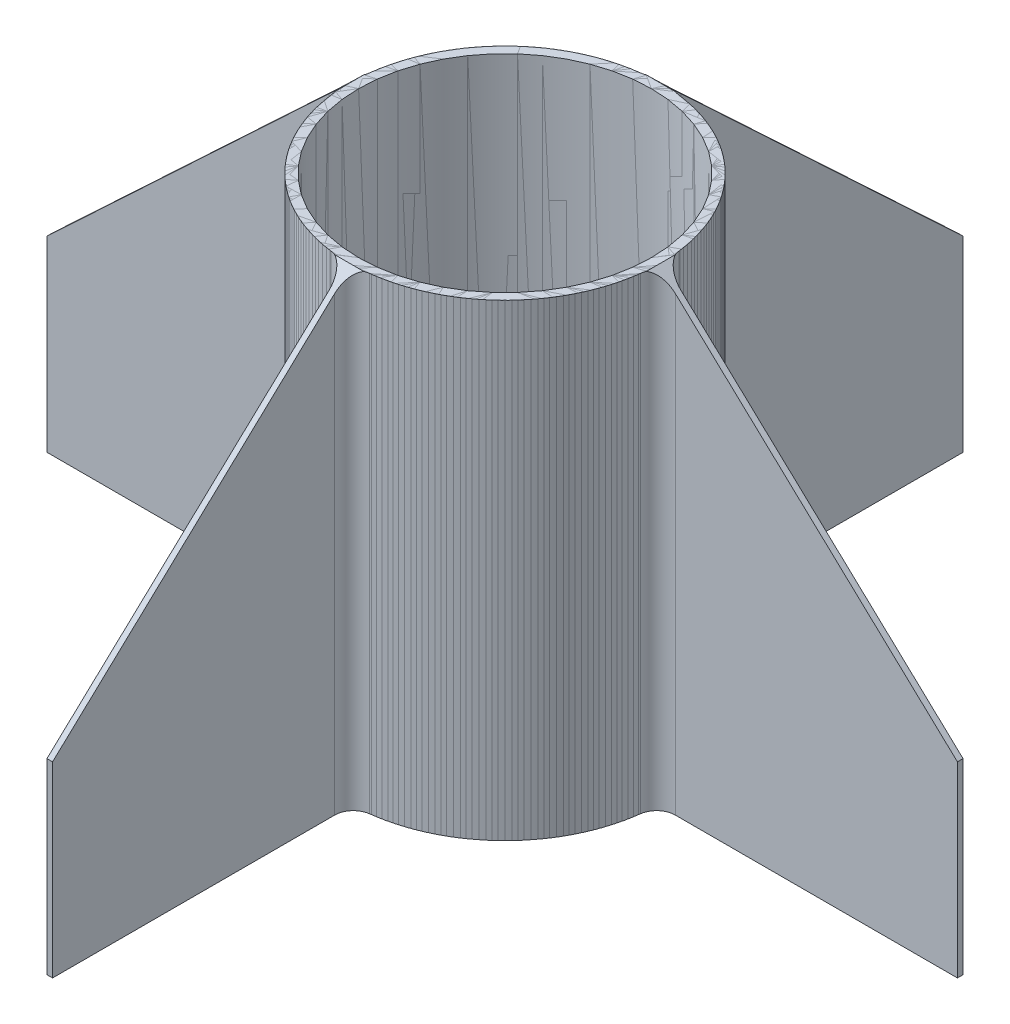
SolidWorks part; units mm, degrees
material "Commercially Pure grade 2 longitudinal (SS)"
ref_plane "Front Plane" through (0, 0, 0) normal (0, 0, 1) x (1, 0, 0)
ref_plane "Top Plane" through (0, 0, 0) normal (0, 1, 0) x (1, 0, 0)
ref_plane "Right Plane" through (0, 0, 0) normal (1, 0, 0) x (0, 0, -1)
sketch "Sketch1" plane through (0, 0, 0) normal (0, 1, 0) x (1, 0, 0)
  circle A0 centre (0, 0) radius 83.2
  circle A1 centre (0, 0) radius 78.2
  dimension "D1" = 166.4
  dimension "D2" = 156.4
extrude "Boss-Extrude1" add sketch "Sketch1" along normal blind 250
sketch "Sketch2" plane through (0, 0, 0) normal (0, 0, 1) x (1, 0, 0)
  line L0 (83.2, 0) -> (83.2, 250) construction
  line L1 (83.2, 0) -> (83.2, 250)
  line L2 (83.2, 0) -> (243.2, 0)
  line L3 (243.2, 0) -> (243.2, 100)
  line L4 (243.2, 100) -> (83.2, 250)
  dimension "D1" = 160
  dimension "D2" = 100
extrude "Boss-Extrude2" add sketch "Sketch2" along normal blind 1.5 and the other way blind 1.5 separate body
sketch "Sketch4" plane through (0, 0, 0) normal (0, 0, 1) x (1, 0, 0)
  line L0 (83.2, 250) -> (83.2, 0) construction
  line L1 (83.2, 250) -> (83.2, 0)
  line L2 (83.2, 250) -> (81.2, 250)
  line L3 (83.2, 250) -> (-83.2, 250) construction
  line L4 (81.2, 250) -> (81.2, 0)
  line L5 (-83.2, 0) -> (83.2, 0) construction
  line L6 (81.2, 0) -> (83.2, 0)
  point P2 (83.2, 125)
  dimension "D1" = 2
extrude "Boss-Extrude3" add sketch "Sketch4" along normal blind 1.5 and the other way blind 1.5
fillet "Fillet1" radius 10 2 edges at (83.1865, 125, -1.5) (83.1865, 125, 1.5)
pattern_circular "CirPattern1" count 4 over 360 about axis through (0, 250, 0) along (0, -1, 0) of bodies 103
